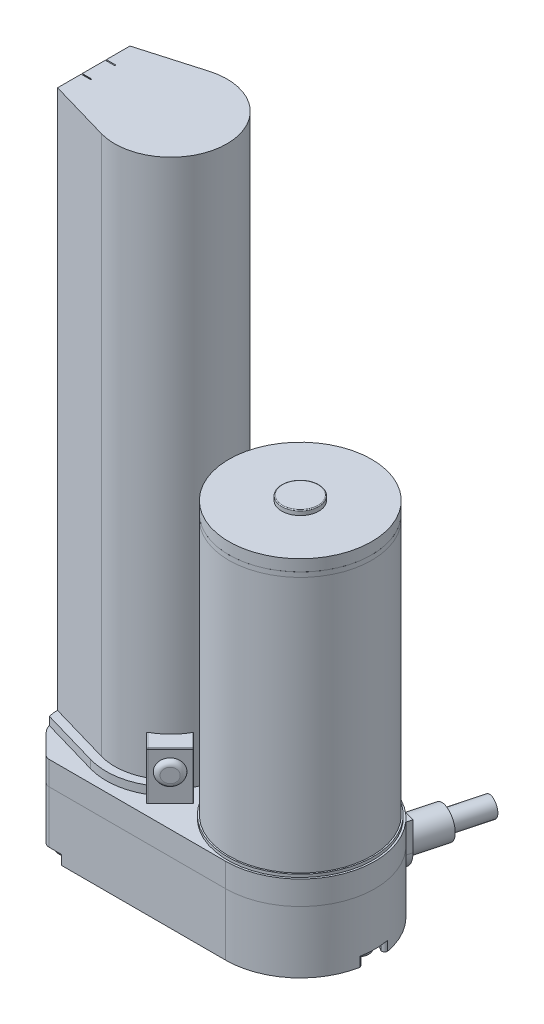
SolidWorks part; units mm, degrees
note: The reader was unsure of these and kept them because the rebuilt part matched: shared geometry of "Sketch1<3>", "Sketch41<11>", "Sketch41<12>", "Sketch45<3>".
ref_plane "Front Plane" through (0, 0, 0) normal (0, 0, 1) x (1, 0, 0)
ref_plane "Top Plane" through (0, 0, 0) normal (0, 1, 0) x (1, 0, 0)
ref_plane "Right Plane" through (0, 0, 0) normal (1, 0, 0) x (0, 0, -1)
sketch "Sketch1" plane through (0, 0, 0) normal (0, 1, 0) x (1, 0, 0)
  line L0 (0, 32.639) -> (7.239, 39.878)
  line L1 (7.239, 0) -> (55.118, 0)
  line L2 (0, 7.239) -> (0, 32.639)
  line L3 (7.239, 39.878) -> (55.118, 39.878)
  line L4 (7.239, 0) -> (0, 7.239)
  arc A0 (55.118, 0) -> (55.118, 39.878) centre (55.118, 19.939) ccw
  point P0 (0, 0)
  point P2 (0, 39.878)
  dimension "D1" = 55.118
  dimension "D2" = 39.878
extrude "Boss-Extrude1" add sketch "Sketch1" along normal blind 6.35
sketch "Sketch6" plane through (0, 6.35, 0) normal (0, 1, 0) x (1, 0, 0)
  circle A0 centre (55.118, 19.939) radius 19.431
extrude "Boss-Extrude4" add sketch "Sketch6" along normal blind 0.762 separate body contours A0
sketch "Sketch7" plane through (0, 7.112, 0) normal (0, 1, 0) x (1, 0, 0)
  circle A0 centre (55.118, 19.939) radius 19.05
  dimension "D1" = 38.1
extrude "Boss-Extrude5" add sketch "Sketch7" along normal blind 68.326 separate body
sketch "Sketch8" plane through (0, 75.438, 0) normal (0, 1, 0) x (1, 0, 0)
  circle A0 centre (55.118, 19.939) radius 4.953
  dimension "D1" = 9.906
fillet "Fillet6" radius 5.08 2 edges at (0, 3.175, -7.239) (0, 3.175, -32.639)
fillet "Fillet7" radius 1.905 2 edges at (7.239, 3.175, -39.878) (7.239, 3.175, 0)
sketch "Sketch15" plane through (0, 6.35, 0) normal (0, 1, 0) x (1, 0, 0)
  line L0 (35.5603, 29.0153) -> (35.5603, 29.0265)
  line L2 (0, 30.5348) -> (0, 9.3432) construction
  line L3 (0, 19.939) -> (0, 10.2869)
  line L4 (0, 19.939) -> (0, 29.591)
  line L5 (0, 10.2869) -> (16.412, 5.5423)
  line L7 (35.5603, 10.8628) -> (35.5603, 10.8515)
  line L10 (0, 29.591) -> (16.4119, 34.3357)
  arc A0 (16.412, 5.5423) -> (16.4119, 34.3357) centre (20.574, 19.939) ccw
ref_plane "Plane4" through (13.8375, 0, -51.6424) normal (0.2588, 0, -0.9659) x (0, -1, 0)
ref_plane "Plane5" through (12.5227, 0, -46.7355) normal (0.2588, 0, -0.9659) x (0, -1, 0)
sketch "Sketch23" plane through (12.5227, 0, -46.7355) normal (0.2588, 0, -0.9659) x (0, -1, 0)
  line L0 (-6.35, -67.5103) -> (-6.35, -28.6483) construction
  line L1 (-2.032, -53.8839) -> (5.588, -53.8839)
  line L2 (-2.032, -53.8839) -> (-2.032, -42.4539)
  line L3 (-2.032, -42.4539) -> (5.588, -42.4539)
  arc A0 (5.588, -53.8839) -> (5.588, -42.4539) centre (5.588, -48.1689) ccw
  dimension "D1" = 11.43
  dimension "D2" = 7.62
  dimension "D3" = 4.318
extrude "Boss-Extrude15" add sketch "Sketch23" along normal blind 6.35
sketch "Sketch24" plane through (14.1662, 0, -52.8692) normal (0.2588, 0, -0.9659) x (-0.9659, 0, -0.2588)
  circle A0 centre (-48.1689, -5.588) radius 4.064
  dimension "D1" = 8.128
extrude "Boss-Extrude16" add sketch "Sketch24" along normal blind 10.16
sketch "Sketch25" plane through (16.7959, 0, -62.683) normal (0.2588, 0, -0.9659) x (-0.9659, 0, -0.2588)
  circle A0 centre (-48.1689, -5.588) radius 2.54
  dimension "D1" = 5.08
extrude "Boss-Extrude17" add sketch "Sketch25" along normal blind 10.16
extrude "Boss-Extrude19" add sketch "Sketch1<3>" against normal blind 16.51 separate body
sketch "Sketch1<3>" plane through (0, 0, 0) normal (0, 1, 0) x (1, 0, 0) same geometry as "Sketch1"
fillet "Fillet13" radius 1.905 2 edges at (7.239, -8.255, 0) (7.239, -8.255, -39.878)
fillet "Fillet14" radius 5.08 2 edges at (0, -8.255, -32.639) (0, -8.255, -7.239)
sketch "Sketch26" plane through (0, -16.51, 0) normal (0, -1, 0) x (-1, 0, 0)
  line L4 (-20.574, 28.829) -> (-11.684, 28.829)
  line L5 (-20.574, 28.829) -> (-29.464, 28.829)
  line L6 (-11.684, 28.829) -> (-11.684, 11.049)
  line L7 (-11.684, 11.049) -> (-29.464, 11.049)
  line L8 (-29.464, 11.049) -> (-29.464, 28.829)
extrude "Boss-Extrude20" add sketch "Sketch26" along normal blind 18.796 separate body
chamfer "Chamfer1" distance 2.54 angle 45 4 edges at (29.464, -25.908, -28.829) (29.464, -25.908, -11.049) (11.684, -25.908, -11.049) (11.684, -25.908, -28.829)
fillet "Fillet15" radius 2.54 8 edges at (11.684, -25.908, -13.589) (14.224, -25.908, -11.049) (26.924, -25.908, -11.049) (29.464, -25.908, -13.589) (29.464, -25.908, -26.289) (26.924, -25.908, -28.829) (11.684, -25.908, -26.289) (14.224, -25.908, -28.829)
chamfer "Chamfer2" distance 0.762 angle 45 16 edges at (14.3041, -35.306, -11.2423) (20.574, -35.306, -11.049) (26.8439, -35.306, -11.2423) (28.194, -35.306, -12.319) (29.2707, -35.306, -13.6691) (29.464, -35.306, -19.939) (29.2707, -35.306, -26.2089) (28.194, -35.306, -27.559) (26.8439, -35.306, -28.6357) (20.574, -35.306, -28.829) (14.3041, -35.306, -28.6357) (12.954, -35.306, -27.559) (11.8773, -35.306, -26.2089) (11.684, -35.306, -19.939) (11.8773, -35.306, -13.6691) (12.954, -35.306, -12.319)
sketch "Sketch27" plane through (0, 0, -11.049) normal (0, 0, 1) x (1, 0, 0)
  circle A0 centre (20.574, -26.67) radius 3.175
extrude "Cut-Extrude3" cut sketch "Sketch27" against normal blind 19.05
sketch "Sketch28" plane through (0, 75.438, 0) normal (0, 1, 0) x (1, 0, 0)
  circle A0 centre (55.118, 19.939) radius 19.05
extrude "Boss-Extrude22" add sketch "Sketch28" along normal blind 1.27 separate body
sketch "Sketch29" plane through (0, 76.708, 0) normal (0, 1, 0) x (1, 0, 0)
  circle A0 centre (55.118, 19.939) radius 19.05
extrude "Boss-Extrude24" add sketch "Sketch29" along normal blind 3.048 separate body contours A0
extrude "Boss-Extrude25" add sketch "Sketch8" along normal blind 1.27 from surface at 4.318 contours A0 starting at face at (55.118, 79.756, -0.889)
fillet "Fillet16" radius 0.2286 1 edges at (55.118, 81.026, -14.986)
extrude "Boss-Extrude26" add sketch "Sketch15" along normal blind 152.781 separate body contours L5 A0 L10 L4 L3
sketch "Sketch32" plane through (0, 159.131, 0) normal (0, 1, 0) x (1, 0, 0)
  line L0 (0, 10.2869) -> (0, 29.591)
  line L1 (0, 29.591) -> (16.4119, 34.3357)
  line L2 (0, 10.2869) -> (16.412, 5.5423)
  arc A0 (16.412, 5.5423) -> (16.4119, 34.3357) centre (20.574, 19.939) ccw
extrude "Boss-Extrude27" add sketch "Sketch32" along normal blind 8.89 separate body
sketch "Sketch33" plane through (0, 168.021, 0) normal (0, 1, 0) x (1, 0, 0)
  circle A0 centre (20.574, 19.939) radius 9.906
extrude "Boss-Extrude28" add sketch "Sketch33" along normal blind 21.336
sketch3d "3DSketch1" plane through (0, 0, 0) normal (0, 0, 1) x (1, 0, 0)
sketch "Sketch41" plane through (0, 6.35, 0) normal (0, 1, 0) x (1, 0, 0)
  line L0 (16.4119, 34.3357) -> (0, 29.591)
  line L1 (37.5429, 9.0662) -> (33.7712, 12.8379)
  line L2 (0.2737, 32.0497) -> (15.777, 36.5318)
  line L3 (37.5429, 9.0662) -> (31.2567, 2.78)
  line L4 (0, 29.591) -> (0, 30.5348)
  line L5 (0, 30.5348) -> (0.2737, 32.0497)
  line L6 (-0.6349, 31.7871) -> (15.777, 36.5318) construction
  line L7 (0, 19.9389) -> (7.9017, 19.9389)
  line L8 (31.2567, 2.78) -> (27.426, 6.6107)
  line L9 (0, 10.2869) -> (0, 29.591) construction
  line L10 (0, 10.2869) -> (0, 9.3431)
  line L12 (37.5429, 30.8116) -> (33.7712, 27.0399)
  line L13 (37.5429, 30.8116) -> (31.2567, 37.0978)
  line L14 (31.2567, 37.0978) -> (27.426, 33.2671)
  line L15 (0, 9.3431) -> (0.2737, 7.8281)
  line L16 (0.2737, 7.8281) -> (15.777, 3.3461)
  line L17 (16.4119, 5.5422) -> (0, 10.2869)
  line L18 (-0.6349, 8.0908) -> (15.7771, 3.3462) construction
  line L19 (27.426, 33.2671) -> (29.1122, 34.9533)
  line L20 (0, 29.591) -> (16.4119, 34.3357) construction
  line L21 (0, 10.2869) -> (16.412, 5.5423) construction
  arc A0 (16.4119, 34.3357) -> (33.7712, 27.0399) centre (20.574, 19.939) cw
  arc A1 (15.777, 36.5318) -> (29.1122, 34.9533) centre (20.574, 19.939) cw
  arc A2 (16.4119, 34.3357) -> (16.412, 5.5423) centre (20.574, 19.939) cw construction
  arc A3 (15.777, 36.5318) -> (15.7771, 3.3462) centre (20.574, 19.939) cw construction
  arc A4 (16.4119, 34.3357) -> (27.426, 33.2671) centre (20.574, 19.939) cw
  arc A5 (15.777, 3.3461) -> (29.1122, 4.9245) centre (20.574, 19.9389) ccw
  arc A6 (16.4119, 5.5422) -> (33.7712, 12.8379) centre (20.574, 19.9389) ccw
  line M5 (0, 30.5348) -> (0, 9.3432)
  arc M6 (0, 9.3432) -> (1.4879, 5.7511) centre (5.08, 9.3432) ccw
extrude "Boss-Extrude30" add sketch "Sketch41" along normal blind 2.159 separate body contours A1 L2 L5 L0 A0 L14 M5
extrude "Boss-Extrude31" add sketch "Sketch41<11>" along normal blind 2.159 separate body contours A6 L17 L15 L16 A5 L8 M5 M6
sketch "Sketch41<11>" plane through (0, 6.35, 0) normal (0, 1, 0) x (1, 0, 0) same geometry as "Sketch41"
extrude "Boss-Extrude33" add sketch "Sketch41<12>" along normal blind 12.7 separate body contours L14 A0 L12 L13 | A6 L8 L3 L1
sketch "Sketch41<12>" plane through (0, 6.35, 0) normal (0, 1, 0) x (1, 0, 0) same geometry as "Sketch41"
fillet "Fillet17" radius 0.2286 5 edges at (35.657, 19.05, -28.9258) (29.3413, 19.05, -35.1825) (34.3998, 19.05, -33.9547) (37.5429, 12.7, -30.8116) (31.2567, 12.7, -37.0978)
fillet "Fillet18" radius 0.2286 5 edges at (35.657, 19.05, -10.9521) (29.3413, 19.05, -4.6954) (37.5429, 12.7, -9.0662) (34.3998, 19.05, -5.9231) (31.2567, 12.7, -2.78)
sketch "Sketch43" plane through (34.1773, 0, -34.1773) normal (0.7071, 0, -0.7071) x (-0.7071, 0, -0.7071)
  circle A0 centre (-0.3147, 13.7414) radius 3.175
extrude "Boss-Extrude34" add sketch "Sketch43" along normal blind 1.27 separate body
fillet "Fillet19" radius 1.27 1 edges at (33.0527, 13.7414, -37.0978)
sketch "Sketch44" plane through (14.2383, 0, 14.2383) normal (0.7071, 0, 0.7071) x (0.7071, 0, -0.7071)
  circle A0 centre (28.5126, 13.7414) radius 3.175
extrude "Boss-Extrude35" add sketch "Sketch44" along normal blind 1.27 separate body
fillet "Fillet20" radius 1.27 1 edges at (37.5429, 13.7414, -7.2702)
sketch "Sketch45" plane through (0, -16.51, 0) normal (0, -1, 0) x (1, 0, 0)
  line L0 (4.0845, -36.7235) -> (6.681, -39.32)
  line L2 (6.681, -39.32) -> (1.4879, -34.1269) construction
  line L4 (55.118, -39.878) -> (8.0281, -39.878) construction
  line L5 (11.3938, -39.878) -> (8.0281, -39.878)
  line L6 (11.3938, 0) -> (8.0281, 0)
  line L7 (4.0845, -3.1545) -> (6.681, -0.558)
  arc A0 (11.2821, -38.9146) -> (11.3938, -39.878) centre (11.8197, -39.3405) ccw
  arc A1 (11.2821, -38.9146) -> (5.0443, -35.9783) centre (8.8543, -35.9783) ccw
  arc A2 (11.2821, -0.9634) -> (11.3938, 0) centre (11.8197, -0.5375) cw
  arc A3 (5.0443, -35.9783) -> (4.0845, -36.7235) centre (4.1918, -35.871) cw
  arc A4 (5.0443, -3.8997) -> (4.0845, -3.1545) centre (4.1918, -4.007) ccw
  arc A5 (11.2821, -0.9634) -> (5.0443, -3.8997) centre (8.8543, -3.8997) cw
  arc A6 (55.118, -39.878) -> (55.118, 0) centre (55.118, -19.939) ccw construction
  arc A7 (73.6621, -16.9922) -> (73.6621, -22.8858) centre (71.247, -19.939) ccw
  arc A8 (73.6621, -22.8858) -> (74.7121, -23.6317) centre (73.8141, -23.7837) cw
  arc A9 (73.6621, -16.9922) -> (74.7121, -16.2463) centre (73.8141, -16.0943) ccw
  arc A10 (8.0281, -39.878) -> (6.681, -39.32) centre (8.0281, -37.973) cw
  arc A11 (8.0281, 0) -> (6.681, -0.558) centre (8.0281, -1.905) ccw
  arc A12 (74.7121, -23.6317) -> (74.7121, -16.2463) centre (55.118, -19.939) ccw
  line M8 (1.4879, -34.1269) -> (6.681, -39.32)
  arc M9 (6.681, -39.32) -> (8.0281, -39.878) centre (8.0281, -37.973) ccw
  line M10 (8.0281, -39.878) -> (55.118, -39.878)
  line M12 (55.118, 0) -> (8.0281, 0)
  arc M13 (8.0281, 0) -> (6.681, -0.558) centre (8.0281, -1.905) ccw
  line M14 (6.681, -0.558) -> (1.4879, -5.7511)
extrude "Cut-Extrude5" cut sketch "Sketch45" against normal blind 2.54 contours A1 A3 A0 M8 M9 M10 | A5 A2 A4 M12 M13 M14
extrude "Cut-Extrude6" cut sketch "Sketch45<3>" against normal blind 2.54
sketch "Sketch45<3>" plane through (0, -16.51, 0) normal (0, -1, 0) x (1, 0, 0) same geometry as "Sketch45"
sketch "Sketch47" plane through (0, -13.97, 0) normal (0, -1, 0) x (-1, 0, 0)
  circle A0 centre (-8.8543, 35.9783) radius 2.54
  circle A1 centre (-8.8543, 3.8997) radius 2.54
  circle A2 centre (-71.247, 19.939) radius 2.54
extrude "Boss-Extrude36" add sketch "Sketch47" along normal blind 2.54 separate body
fillet "Fillet22" radius 1.524 1 edges at (8.8543, -16.51, -38.5183)
fillet "Fillet23" radius 1.524 1 edges at (8.8543, -16.51, -6.4397)
sketch "Sketch48" plane through (0, 0, 0) normal (-1, 0, 0) x (0, 0, 1)
  circle A0 centre (-19.939, 12.7) radius 3.81
extrude "Boss-Extrude37" add sketch "Sketch48" along normal blind 1.524
fillet "Fillet24" radius 1.524 1 edges at (-1.524, 12.7, -16.129)
fillet "Fillet25" radius 1.524 1 edges at (71.247, -16.51, -22.479)
sketch "Sketch49" plane through (0, 0, 0) normal (-1, 0, 0) x (0, 0, 1)
  line L0 (-19.9389, 159.131) -> (-19.9389, 154.178) construction
  line L1 (-29.591, 159.131) -> (-10.2869, 159.131) construction
  line L2 (-30.5348, 6.35) -> (-9.3432, 6.35) construction
  circle A0 centre (-19.9389, 154.178) radius 3.81
  dimension "Flat Head Screw" = 147.828
extrude "Cut-Extrude7" cut sketch "Sketch49" against normal blind 2.54
sketch "Sketch50" plane through (2.54, 0, 0) normal (-1, 0, 0) x (0, 0, 1)
  circle A0 centre (-19.9389, 154.178) radius 3.556
extrude "Boss-Extrude39" add sketch "Sketch50" along normal blind 2.54 contours A0
sketch "Sketch52" plane through (0, 0, -11.049) normal (0, 0, 1) x (1, 0, 0)
  circle A0 centre (20.574, 179.832) radius 3.175
  circle A1 centre (20.574, -26.67) radius 3.175 construction
  dimension "Hole to Hole" = 206.502
extrude "Cut-Extrude11" cut sketch "Sketch52" against normal through all both and the other way through all
sketch "Sketch53" plane through (0, 0, 0) normal (0, 0, 1) x (1, 0, 0)
  line L1 (0, -16.51) -> (89.1325, -16.51)
  line L2 (0, -16.51) -> (0, -38.2408)
  line L3 (0, -38.2408) -> (89.1325, -38.2408)
  line L4 (89.1325, -16.51) -> (89.1325, -38.2408)
extrude "Cut-Extrude12" cut sketch "Sketch53" against normal blind 104.394
sketch "Sketch54" plane through (0, 0, 0) normal (0, 0, 1) x (1, 0, 0)
  line L1 (10.668, 189.357) -> (35.5603, 189.357)
  line L2 (10.668, 189.357) -> (10.668, 168.021)
  line L3 (10.668, 168.021) -> (35.5603, 168.021)
  line L4 (35.5603, 189.357) -> (35.5603, 168.021)
extrude "Cut-Extrude13" cut sketch "Sketch54" against normal blind 104.394
sketch "Sketch55" plane through (0, 0, 0) normal (0, 0, 1) x (1, 0, 0)
  line L3 (0, 152.4) -> (78.4053, 152.4)
  line L5 (0, 152.4) -> (78.4053, 152.4)
  line L6 (0, 152.4) -> (0, 169.6937)
  line L7 (0, 169.6937) -> (78.4053, 169.6937)
  line L8 (78.4053, 152.4) -> (78.4053, 169.6937)
extrude "Cut-Extrude14" cut sketch "Sketch55" against normal blind 104.394 contours L3 L8 L7 L6
equation "\"Stroke\"= 4"
equation "\"D1@Boss-Extrude26\"= \"Stroke\" + 2.015"
equation "\"Flat Head Screw@Sketch49\"= \"Stroke\" + 1.82"
equation "\"Hole to Hole@Sketch52\"= \"Stroke\" + 4.13"
